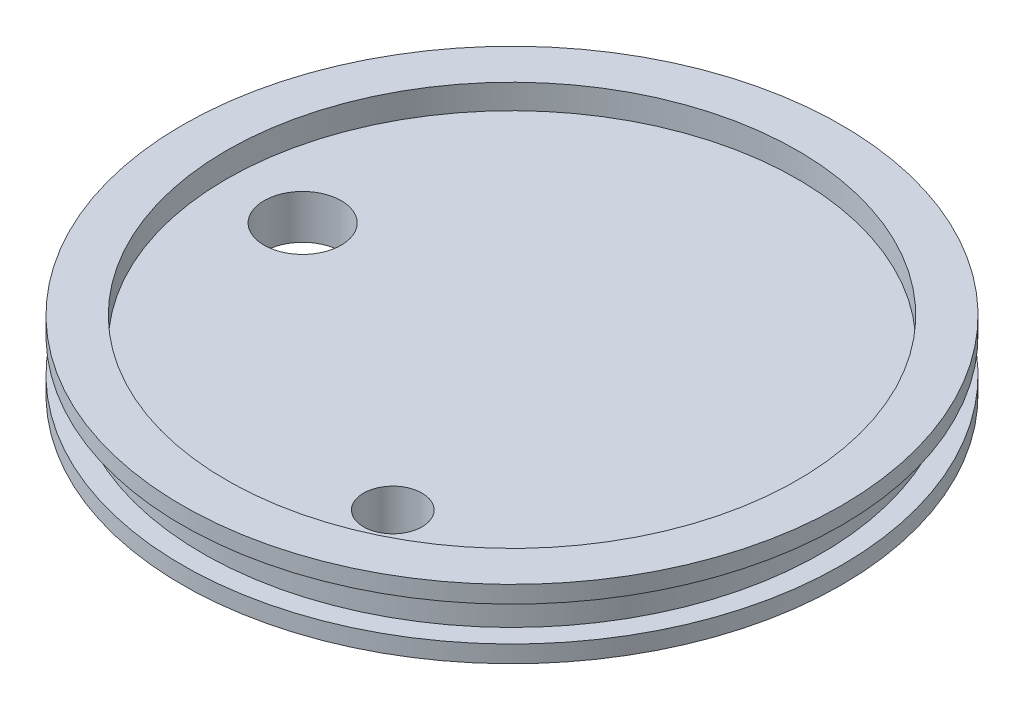
SolidWorks part; units mm, degrees
material "6061-T6 (SS)"
ref_plane "Front Plane" through (0, 0, 0) normal (0, 0, 1) x (1, 0, 0)
ref_plane "Top Plane" through (0, 0, 0) normal (0, 1, 0) x (1, 0, 0)
ref_plane "Right Plane" through (0, 0, 0) normal (1, 0, 0) x (0, 0, -1)
sketch "Sketch1" plane through (0, 0, 0) normal (0, 0, 1) x (1, 0, 0)
  line L0 (0, 48.1922) -> (0, -25.6743) construction
  line L1 (0, 0) -> (47.498, 0)
  line L2 (47.498, 0) -> (47.498, 2.4638)
  line L3 (47.498, 2.4638) -> (44.577, 2.4638)
  line L4 (44.577, 2.4638) -> (44.577, 7.4422)
  line L5 (44.577, 7.4422) -> (47.498, 7.4422)
  line L6 (47.498, 7.4422) -> (47.498, 9.906)
  line L7 (47.498, 9.906) -> (41.148, 9.906)
  line L8 (41.148, 9.906) -> (41.148, 6.35)
  line L9 (41.148, 6.35) -> (0, 6.35)
  line L10 (0, 6.35) -> (0, 0)
  dimension "D1" = 94.996
  dimension "D2" = 4.9784
  dimension "D3" = 2.921
  dimension "D4" = 9.906
  dimension "D5" = 6.35
  dimension "D6" = 6.35
revolve "Revolve1" add sketch "Sketch1" angle 360 about L0
hole_wizard "Pipe Tap Drill for 1/4 Tap1" positions "Sketch2" profile "Sketch3" hole size "1/4" standard "ANSI Inch" end condition through all
sketch "Sketch2" plane through (0, 6.35, 0) normal (0, 1, 0) x (1, 0, 0)
  point P4 (-30.1752, 0)
  dimension "D1" = 30.1752
sketch "Sketch3" plane through (-30.1752, 6.35, 0) normal (1, 0, 0) x (0, 0, 1)
  line L0 (0, 0) -> (0, 6.35)
  line L1 (0, 6.35) -> (5.5626, 6.35)
  line L2 (5.5626, 6.35) -> (5.5626, 0)
  line L5 (5.5626, 0) -> (0, 0)
  line L11 (0, -6.35) -> (0, 107.95) construction
  dimension "Thru Hole Dia." = 11.1252
  dimension "Thru Hole Depth" = 6.35
hole_wizard "Pipe Tap Drill for 1/8 Tap1" positions "Sketch4" profile "Sketch5" hole size "1/8" standard "ANSI Inch" end condition through all
sketch "Sketch4" plane through (0, 6.35, 0) normal (0, 1, 0) x (1, 0, 0)
  line L0 (0, 0) -> (12.1502, -29.3332)
  line L1 (0, 0) -> (0, -37.3592)
  point P16 (12.1502, -29.3332)
  dimension "D1" = 31.75
  dimension "D2" = 22.5
sketch "Sketch5" plane through (12.1502, 6.35, 29.3332) normal (1, 0, 0) x (0, 0, 1)
  line L0 (0, 0) -> (0, 6.35)
  line L1 (0, 6.35) -> (4.2164, 6.35)
  line L2 (4.2164, 6.35) -> (4.2164, 0)
  line L5 (4.2164, 0) -> (0, 0)
  line L11 (0, -6.35) -> (0, 107.95) construction
  dimension "Thru Hole Dia." = 8.4328
  dimension "Thru Hole Depth" = 6.35
fillet "CNC ID Fillet" [suppressed] radius 0.1778
fillet "CNC OD Fillet" [suppressed] radius 0.127
chamfer "CNC Chamfers" [suppressed] distance 0.254 angle 45
fillet "CNC Bore Fillet" [suppressed] radius 0.254
